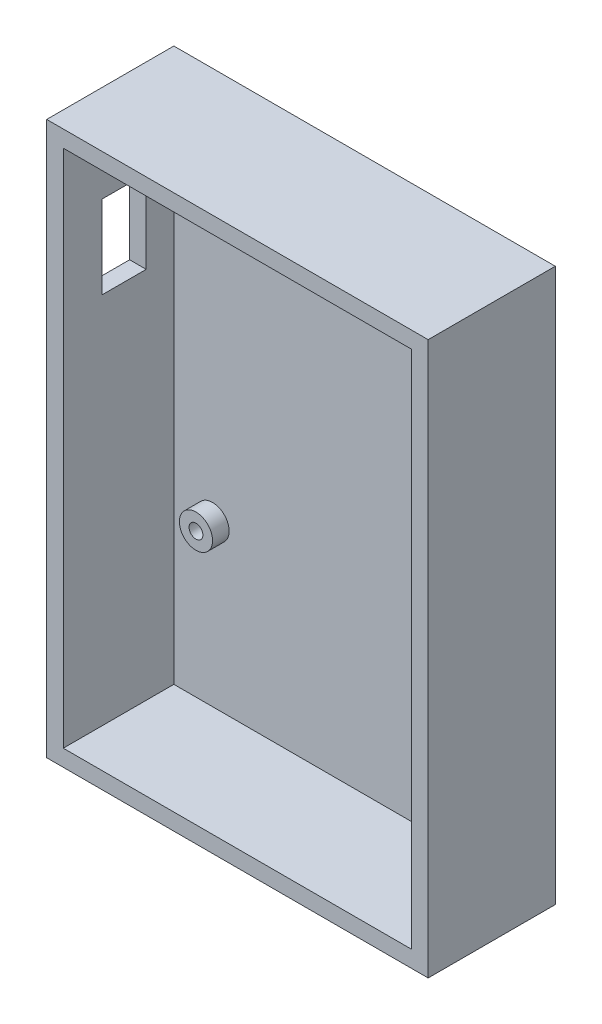
SolidWorks part; units mm, degrees
ref_plane "Ön Düzlem" through (0, 0, 0) normal (0, 0, 1) x (1, 0, 0)
ref_plane "Üst Düzlem" through (0, 0, 0) normal (0, 1, 0) x (1, 0, 0)
ref_plane "Sağ Düzlem" through (0, 0, 0) normal (1, 0, 0) x (0, 0, -1)
sketch "Çizim1" plane through (0, 0, 0) normal (0, 0, 1) x (1, 0, 0)
  line L0 (-34.5, 50) -> (34.5, -50) construction
  line L1 (-34.5, 50) -> (34.5, 50)
  line L2 (-34.5, 50) -> (-34.5, -50)
  line L3 (-34.5, -50) -> (34.5, -50)
  line L4 (34.5, 50) -> (34.5, -50)
  circle A0 centre (0, 31.5805) radius 3
  dimension "D1" = 100
  dimension "D2" = 69
extrude "Yükseklik-Ekstrüzyon1" add sketch "Çizim1" along normal blind 3
sketch "Çizim2" plane through (0, 0, 3) normal (0, 0, 1) x (1, 0, 0)
  line L0 (34.5, 50) -> (-34.5, 50) construction
  line L1 (-34.5, 50) -> (-34.5, -50) construction
  circle A0 centre (-24.5, 40) radius 1.25
  circle A1 centre (-24.5, 40) radius 3
  circle A2 centre (24.5, 40) radius 3
  circle A3 centre (24.5, 40) radius 1.25
  circle A4 centre (24.5, -18) radius 3
  circle A5 centre (24.5, -18) radius 1.25
  circle A6 centre (-24.5, -18) radius 3
  circle A7 centre (-24.5, -18) radius 1.25
  dimension "D1" = 2
  dimension "D3" = 10
  dimension "D4" = 10
  dimension "D2" = 2
extrude "Yükseklik-Ekstrüzyon2" add sketch "Çizim2" along normal blind 3
sketch "Çizim3" plane through (0, 0, 3) normal (0, 0, 1) x (1, 0, 0)
  line L1 (-31.5, 47) -> (-31.5, -47)
  line L2 (-34.5, 50) -> (34.5, 50)
  line L3 (-34.5, 50) -> (-34.5, -50)
  line L4 (-34.5, -50) -> (34.5, -50)
  line L5 (34.5, 50) -> (34.5, -50)
  line L6 (-31.5, -47) -> (31.5, -47)
  line L7 (31.5, 47) -> (31.5, -47)
  line L8 (-31.5, 47) -> (31.5, 47)
  dimension "D1" = 3
extrude "Yükseklik-Ekstrüzyon3" add sketch "Çizim3" along normal blind 20
sketch "Çizim5" plane through (-34.5, 0, 0) normal (-1, 0, 0) x (0, 0, 1)
  line L0 (0, 50) -> (0, -50) construction
  line L1 (8, 35.5114) -> (16, 35.5114)
  line L2 (8, 35.5114) -> (8, 20.5114)
  line L3 (8, 20.5114) -> (16, 20.5114)
  line L4 (16, 35.5114) -> (16, 20.5114)
  dimension "D1" = 8
  dimension "D2" = 15
  dimension "D3" = 8
extrude "Kes-Ekstrüzyon1" cut sketch "Çizim5" against normal blind 10
